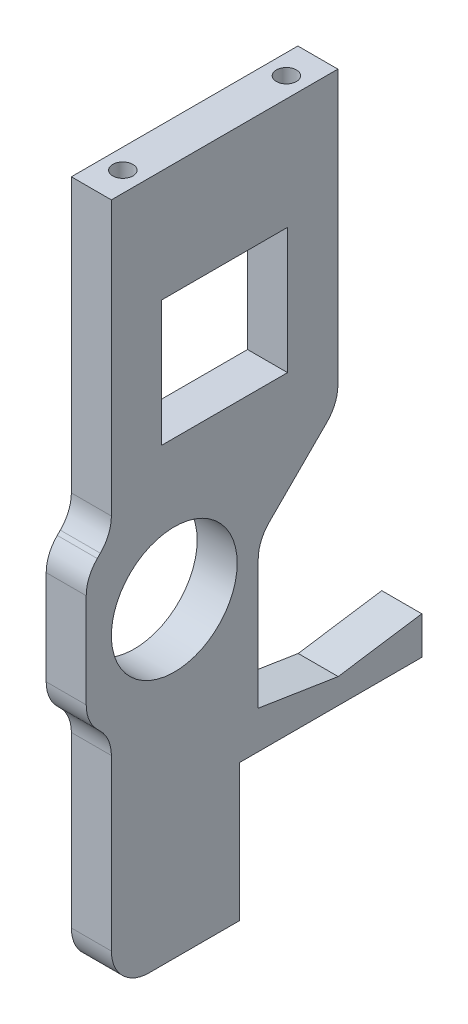
SolidWorks part; units mm, degrees
ref_plane "Front Plane" through (0, 0, 0) normal (0, 0, 1) x (1, 0, 0)
ref_plane "Top Plane" through (0, 0, 0) normal (0, 1, 0) x (1, 0, 0)
ref_plane "Right Plane" through (0, 0, 0) normal (1, 0, 0) x (0, 0, -1)
sketch "Sketch2" plane through (0, 0, 0) normal (1, 0, 0) x (0, 0, -1)
  line L0 (-7.3996, 19.4136) -> (10.6004, 19.4136)
  line L1 (10.6004, 19.4136) -> (10.6004, -3.5864)
  line L2 (2.7704, -35.2864) -> (-7.3996, -35.2864)
  line L3 (-9.3996, -15.5864) -> (-9.3996, -5.5864)
  line L4 (-21.5473, -39.2864) -> (35.9179, -39.2864) construction
  line L14 (-7.3996, -3.5864) -> (-7.3996, 19.4136)
  line L16 (-7.3996, -17.5864) -> (-7.3996, -35.2864)
  line L19 (2.7704, -35.2864) -> (2.7704, -24.4064)
  line L20 (2.7704, -24.4064) -> (17.2704, -24.4064)
  line L25 (-9.3996, -5.5864) -> (-7.3996, -3.5864)
  line L26 (-9.3996, -15.5864) -> (-7.3996, -17.5864)
  line L28 (-2.3996, -5.5864) -> (-9.3996, -5.5864) construction
  line L29 (-2.3996, -15.5864) -> (-9.3996, -15.5864) construction
  line L30 (10.6004, -3.5864) -> (4.2704, -9.9164)
  line L31 (4.2704, -9.9164) -> (4.2704, -21.4064)
  line L38 (4.2704, -21.4064) -> (10.6253, -22.4064)
  line L39 (10.6253, -22.4064) -> (17.2704, -21.4064)
  line L40 (17.2704, -21.4064) -> (17.2704, -24.4064)
  line L42 (-3.3996, 10.5244) -> (6.6004, 10.5244) construction
  line L43 (-3.3996, 10.5244) -> (-3.3996, 0.5244) construction
  line L44 (-3.3996, 0.5244) -> (6.6004, 0.5244) construction
  line L45 (6.6004, 10.5244) -> (6.6004, 0.5244) construction
  circle A1 centre (-2.3996, -10.5864) radius 5
  circle A2 centre (1.6004, 5.5244) radius 8 construction
  circle A3 centre (1.6004, 5.5244) radius 5
  dimension "D1" = 28.7
  dimension "D2" = 2
  dimension "D4" = 18
  dimension "D6" = 16
  dimension "D7" = 10
  dimension "D3" = 10
  dimension "D10" = 2
  dimension "D9" = 2
  dimension "D5" = 16.6
  dimension "D8" = 9
  dimension "D11" = 1
  dimension "D12" = 10.88
  dimension "D13" = 4
  dimension "D14" = 13
  dimension "D15" = 1.5
  dimension "D16" = 10.17
  dimension "D17" = 23
extrude "Boss-Extrude1" add sketch "Sketch2" against normal blind 3.18 contours L0 L1 L30 L31 L38 L39 L40 L20 L19 L2 L16 L26 L3 L25 L14
extrude "Cut-Extrude2" cut sketch "Sketch2<4>" against normal blind 3.18 flip side to cut
sketch "Sketch2<4>" plane through (0, 0, 0) normal (1, 0, 0) x (0, 0, -1) same geometry as "Sketch2"
fillet "Fillet6" radius 3 7 edges at (-1.59, -17.5864, 7.3996) (-1.59, -15.5864, 9.3996) (-1.59, -5.5864, 9.3996) (-1.59, -3.5864, 7.3996) (-1.59, -35.2864, 7.3996) (-1.59, -3.5864, -10.6004) (-1.59, -9.9164, -4.2704)
hole_wizard "M2x0.4 Tapped Hole1" positions "Sketch5" profile "Sketch6" tap size "M2x0.4" standard "ANSI Metric"
sketch "Sketch5" plane through (0, 19.4136, 0) normal (0, 1, 0) x (1, 0, 0)
  line L0 (-3.18, 10.6004) -> (0, 10.6004) construction
  line L1 (-3.18, -7.3996) -> (0, -7.3996) construction
  line L2 (0, -7.3996) -> (0, 10.6004) construction
  point P0 (-1.59, 8.1004)
  point P2 (-1.59, -4.8996)
  point P13 (-1.59, 8.1004)
  dimension "D1" = 2.5
  dimension "D2" = 2.5
  dimension "D3" = 1.59
sketch "Sketch6" plane through (-1.59, 19.4136, -8.1004) normal (1, 0, 0) x (0, 0, 1)
  line L0 (0, 0) -> (0, 6)
  line L1 (0, 6) -> (0.8, 5.5193)
  line L2 (0.8, 5.5193) -> (0.8, 0)
  line L5 (0.8, 0) -> (0, 0)
  line L10 (0, 6) -> (-0.8, 5.5193) construction
  line L11 (0, -6.35) -> (0, 107.95) construction
  dimension "Tap Drill Dia." = 1.6
  dimension "Tap Drill Depth" = 6
  dimension "Drill Angle" = 118
mirror "Mirror1" about plane through (0, 0, 0) normal (-1, 0, 0) of bodies 104
delete or keep bodies "Body-Delete/Keep 1" type delete bodies bodies 104
sketch "Sketch10" plane through (3.18, 0, 0) normal (1, 0, 0) x (0, 0, -1)
  line L1 (6.6004, 10.5244) -> (-3.3996, 10.5244)
  line L2 (6.6004, 10.5244) -> (6.6004, 0.5244)
  line L3 (6.6004, 0.5244) -> (-3.3996, 0.5244)
  line L4 (-3.3996, 10.5244) -> (-3.3996, 0.5244)
extrude "Cut-Extrude4" cut sketch "Sketch10" against normal blind 10
equation "\"RollerToBaseplate\"= 28.7mm"
equation "\"SteelShaftDia\"= 10mm"
equation "\"DribblerMotorDia\"= 16mm"
equation "\"DribblerHeight\"= 50mm"
